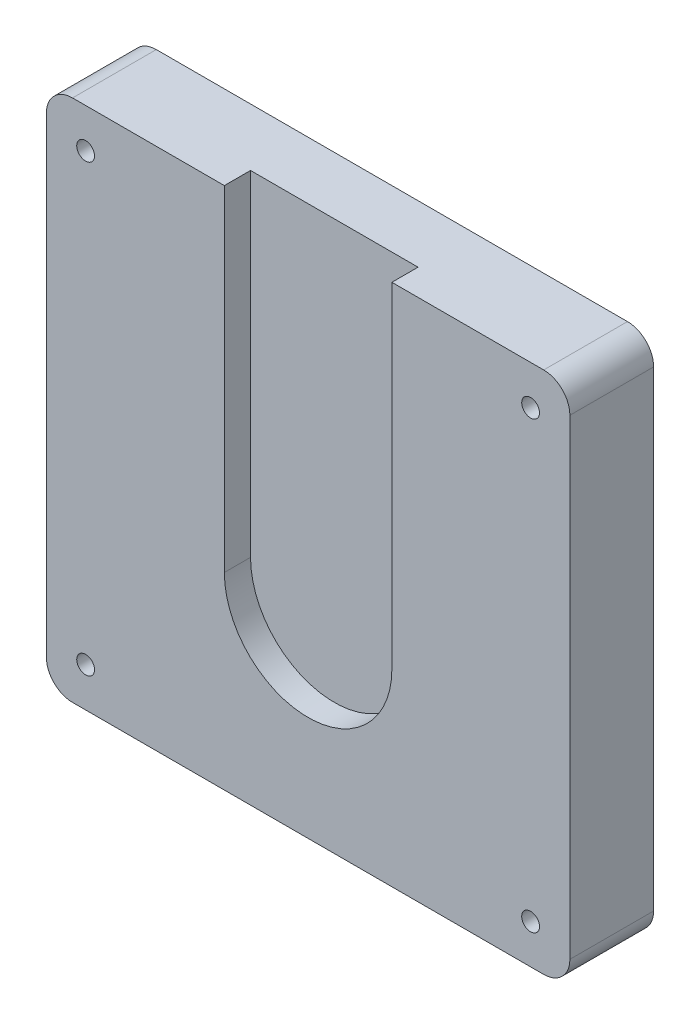
SolidWorks part; units mm, degrees
ref_plane "Front Plane" through (0, 0, 0) normal (0, 0, 1) x (1, 0, 0)
ref_plane "Top Plane" through (0, 0, 0) normal (0, 1, 0) x (1, 0, 0)
ref_plane "Right Plane" through (0, 0, 0) normal (1, 0, 0) x (0, 0, -1)
sketch "Sketch1" plane through (0, 0, 0) normal (0, 0, 1) x (1, 0, 0)
  line L0 (-50, 50) -> (50, -50) construction
  line L1 (-50, -50) -> (50, -50)
  line L2 (-50, -50) -> (-50, 50)
  line L3 (-50, 50) -> (50, 50)
  line L4 (50, -50) -> (50, 50)
  dimension "D1" = 100
  dimension "D2" = 100
extrude "Boss-Extrude1" add sketch "Sketch1" along normal blind 16 contours L4 L3 L2 L1
sketch "Sketch2" plane through (0, 0, 16) normal (0, 0, 1) x (1, 0, 0)
  line L4 (-50, -50) -> (50, -50)
  line L5 (50, -50) -> (50, 50)
  line L6 (50, 50) -> (-50, 50)
  line L7 (-50, 50) -> (-50, -50)
  line L8 (-50, -50) -> (50, -50)
  line L9 (50, -50) -> (50, 50)
  line L10 (50, 50) -> (-50, 50)
  line L11 (-50, 50) -> (-50, -50)
  dimension "D1" = 0
extrude "Boss-Extrude2" add sketch "Sketch2" along normal blind 16 separate body
sketch "Sketch3" plane through (0, 50, 0) normal (0, 1, 0) x (1, 0, 0)
  line L21 (-16, -32) -> (-16, -28.5)
  line L23 (50, -32) -> (-50, -32) construction
  line L24 (-16, -28.5) -> (-10, -28.5)
  line L25 (-10, -28.5) -> (-10, -16)
  line L26 (-10, -16) -> (-16, -16)
  line L27 (-16, -16) -> (-16, -11)
  line L28 (-16, -11) -> (16, -11)
  line L29 (-16, -32) -> (16, -32)
  line L30 (0, -32) -> (0, 0) construction
  line L31 (16, -16) -> (16, -11)
  line L32 (10, -16) -> (16, -16)
  line L33 (10, -28.5) -> (10, -16)
  line L34 (16, -28.5) -> (10, -28.5)
  line L35 (16, -32) -> (16, -28.5)
  point P17 (0, -11)
  dimension "D1" = 3.5
  dimension "D2" = 12.5
  dimension "D3" = 5
  dimension "D4" = 32
  dimension "D5" = 32
  dimension "D6" = 20
extrude "Cut-Extrude1" cut sketch "Sketch3" against normal blind 80
sketch "Sketch4" plane through (0, 0, 32) normal (0, 0, 1) x (1, 0, 0)
  line L0 (-16, -30) -> (16, -30) construction
  line L9 (-16, -30) -> (-16, 50)
  line L10 (-16, 50) -> (-50, 50)
  line L11 (-50, 50) -> (-50, -50)
  line L12 (-50, -50) -> (50, -50)
  line L13 (50, -50) -> (50, 50)
  line L14 (50, 50) -> (16, 50)
  line L15 (16, 50) -> (16, -30)
  line L16 (16, -30) -> (-16, -30)
  line L17 (-16, -30) -> (-16, -14)
  line L23 (16, -14) -> (16, -30)
  line L24 (16, -30) -> (-16, -30)
  arc A0 (-16, -14) -> (16, -14) centre (0, -14) ccw
  line M10 (-16, -30) -> (-16, 50)
  line M16 (16, 50) -> (16, -30)
  line M17 (16, -30) -> (-16, -30)
  dimension "D1" = 0
extrude "Boss-Extrude3" add sketch "Sketch4" against normal blind 16 contours A0 L24 M10 | A0 M17 M16 region at (-12.4261, -26.4261, 32) region at (12.4261, -26.4261, 32)
sketch "Sketch5" plane through (0, 0, 11) normal (0, 0, 1) x (1, 0, 0)
  line L7 (16, 50) -> (-16, 50)
  line L8 (-16, 50) -> (-16, -30)
  line L9 (-16, -30) -> (16, -30)
  line L10 (16, -30) -> (16, 50)
  line L12 (-16, -14) -> (-16, -30)
  line L13 (-16, -30) -> (16, -30)
  line L14 (16, -30) -> (16, -14)
  arc A1 (-16, -14) -> (16, -14) centre (0, -14) ccw construction
  arc A2 (-16, -14) -> (16, -14) centre (0, -14) ccw
  line M6 (-16, 50) -> (-16, -30)
  line M7 (-16, -30) -> (16, -30)
  line M8 (16, -30) -> (16, 50)
  dimension "D1" = 0
extrude "Boss-Extrude4" add sketch "Sketch5" along normal up to body separate body contours A2 L13 M8 | A2 M6 M7 region at (12.4261, -26.4261, 11) region at (-12.4261, -26.4261, 11)
hole_wizard "CSK for M3 Countersunk Flat Head Screw1" positions "Sketch6" profile "Sketch7" countersink size "M3" standard "ISO" end condition through all
sketch "Sketch6" plane through (0, 0, 32) normal (0, 0, 1) x (1, 0, 0)
  line L1 (-42.5, 42.5) -> (42.5, 42.5)
  line L2 (-42.5, 42.5) -> (-42.5, -42.5)
  line L3 (-42.5, -42.5) -> (42.5, -42.5)
  line L4 (42.5, 42.5) -> (42.5, -42.5)
  line L5 (0, 42.5) -> (0, 0) construction
  line L6 (0, 0) -> (42.5, 0) construction
  line L8 (-50, 50) -> (-50, -50) construction
  line L9 (-16, 50) -> (-50, 50) construction
  point P0 (-42.5, 42.5)
  point P2 (42.5, 42.5)
  point P4 (42.5, -42.5)
  point P6 (-42.5, -42.5)
  dimension "D1" = 7.5
  dimension "D2" = 7.5
sketch "Sketch7" plane through (-42.5, 42.5, 32) normal (1, 0, 0) x (0, -1, 0)
  line L0 (0, 0) -> (0, 32)
  line L1 (0, 32) -> (1.7, 32)
  line L2 (1.7, 32) -> (1.7, 1.45)
  line L3 (1.7, 1.45) -> (3.15, 0)
  line L5 (3.15, 0) -> (0, 0)
  line L6 (-1.7, 1.45) -> (-3.15, 0) construction
  line L11 (0, -6.35) -> (0, 107.95) construction
  dimension "Thru Hole Dia." = 3.4
  dimension "Thru Hole Depth" = 32
  dimension "Near C'Sink Dia." = 6.3
  dimension "Near C'Sink Angle" = 90
fillet "Fillet1" radius 5 4 edges at (-50, -50, 24) (50, -50, 24) (50, 50, 24) (-50, 50, 24)
fillet "Fillet2" radius 5 4 edges at (50, -50, 8) (50, 50, 8) (-50, 50, 8) (-50, -50, 8)
delete or keep bodies "Body-Delete/Keep 1" type keep bodies bodies 112
delete or keep bodies "Body-Delete/Keep 2" [suppressed] type keep bodies bodies 111
